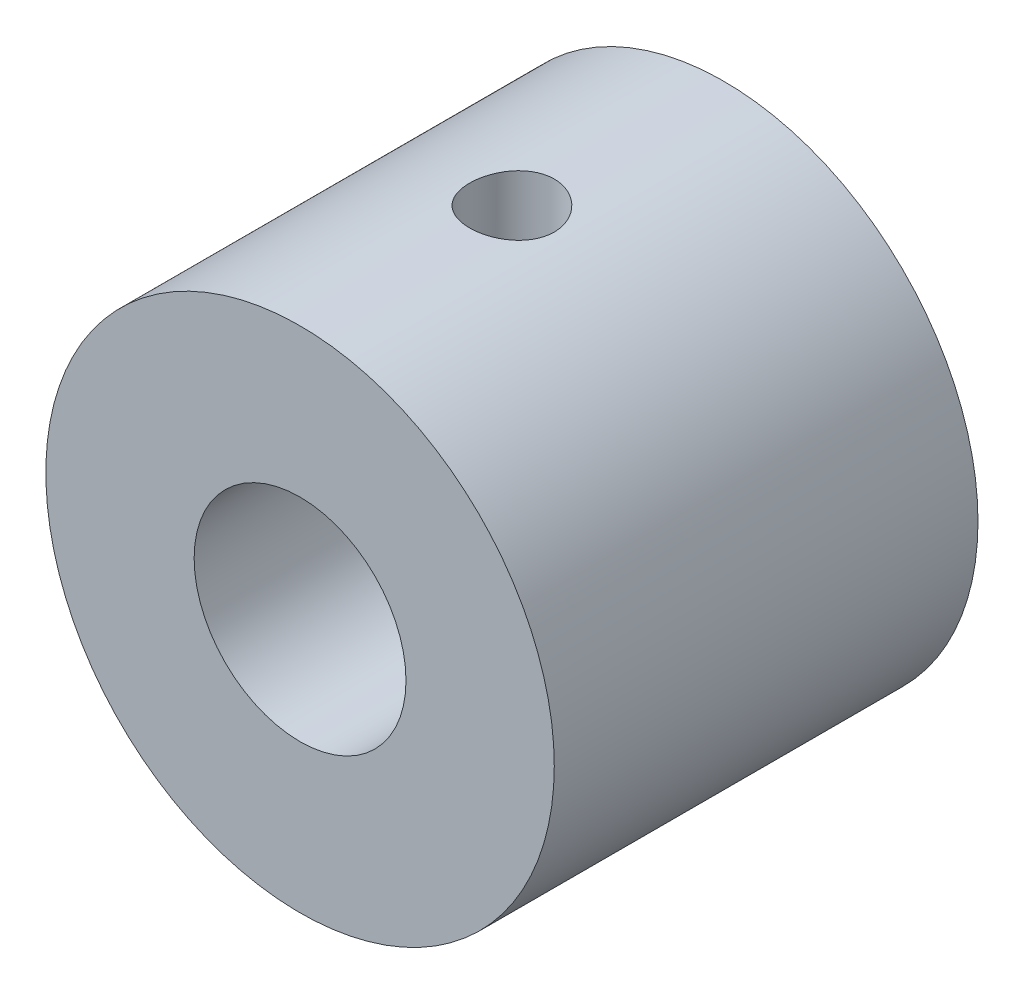
SolidWorks part; units mm, degrees
material "3.3547 (EN-AW 5083)"
ref_plane "Ebene vorne" through (0, 0, 0) normal (0, 0, 1) x (1, 0, 0)
ref_plane "Ebene oben" through (0, 0, 0) normal (0, 1, 0) x (1, 0, 0)
ref_plane "Ebene rechts" through (0, 0, 0) normal (1, 0, 0) x (0, 0, -1)
sketch "Skizze1" plane through (0, 0, 0) normal (0, 0, 1) x (1, 0, 0)
  circle A0 centre (0, 0) radius 2.5
  circle A1 centre (0, 0) radius 6
extrude "Aufsatz-Linear austragen1" add sketch "Skizze1" along normal blind 10
sketch "Skizze2" plane through (0, 0, 0) normal (0, 1, 0) x (1, 0, 0)
  circle A0 centre (0, -5) radius 1
extrude "Schnitt-Linear austragen1" cut sketch "Skizze2" against normal blind 10 and the other way blind 10
